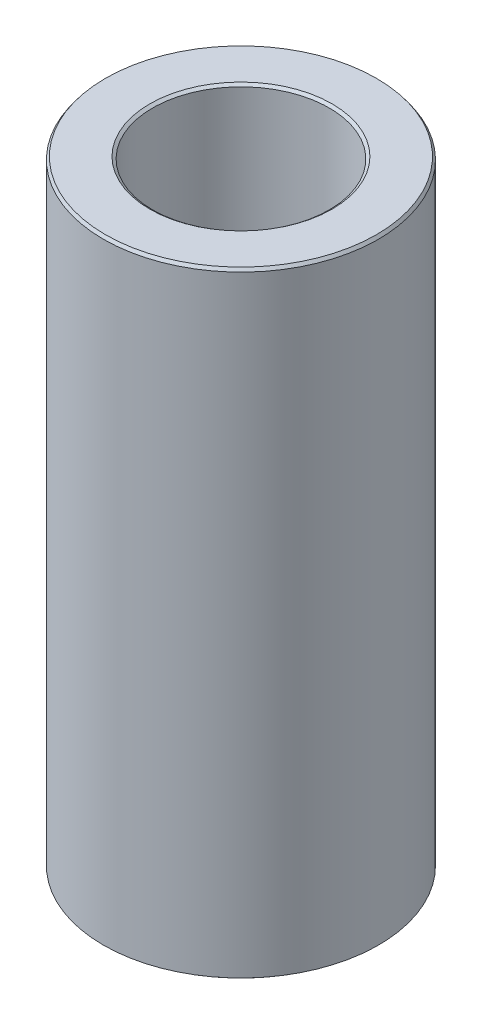
SolidWorks part; units mm, degrees
ref_plane "Front Plane" through (0, 0, 0) normal (0, 0, 1) x (1, 0, 0)
ref_plane "Top Plane" through (0, 0, 0) normal (0, 1, 0) x (1, 0, 0)
ref_plane "Right Plane" through (0, 0, 0) normal (1, 0, 0) x (0, 0, -1)
sketch "Sketch1" plane through (0, 0, 0) normal (0, 1, 0) x (1, 0, 0)
  circle A0 centre (0, 0) radius 37.5
  dimension "SLEEVE_OD" = 75
extrude "Boss-Extrude1" add sketch "Sketch1" along normal blind 168.0043
sketch "Sketch2" plane through (0, 0, 0) normal (0, 1, 0) x (1, 0, 0)
  circle A0 centre (0, 0) radius 24.0759
  dimension "BORE_D" = 48.1517
extrude "Cut-Extrude1" cut sketch "Sketch2" along normal through all
chamfer "Chamfer1" distance 0.7849 angle 36.006 4 edges at (0, 168.0043, 24.0759) (0, 0, 24.0759) (0, 0, 37.5) (0, 168.0043, 37.5) first distance on face at (0, 168.0043, 24.0759) first distance on face at (0, 0, 24.0759) first distance on face at (0, 168.0043, 37.5)
